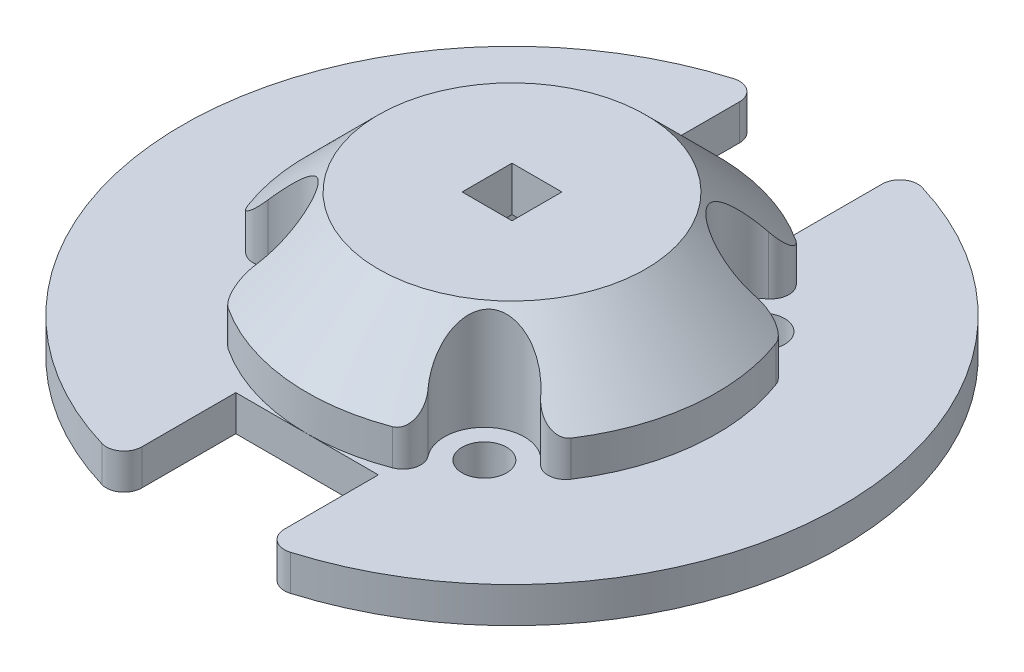
SolidWorks part; units mm, degrees
ref_plane "Front" through (0, 0, 0) normal (0, 0, 1) x (1, 0, 0)
ref_plane "Top" through (0, 0, 0) normal (0, 1, 0) x (1, 0, 0)
ref_plane "Right" through (0, 0, 0) normal (1, 0, 0) x (0, 0, -1)
sketch "Sketch1" plane through (0, 0, 0) normal (0, 1, 0) x (1, 0, 0)
  circle A0 centre (0, 0) radius 12.5
  dimension "D1" = 25
extrude "Boss-Extrude1" add sketch "Sketch1" along normal blind 2
sketch "Sketch2" plane through (0, 2, 0) normal (0, 1, 0) x (1, 0, 0)
  circle A0 centre (0, 0) radius 11.5
  dimension "D1" = 23
extrude "Boss-Extrude2" add sketch "Sketch2" along normal blind 6
sketch "Sketch3" plane through (0, 8, 0) normal (0, 1, 0) x (1, 0, 0)
  line L1 (-1.4, 1.4) -> (1.4, 1.4)
  line L2 (-1.4, 1.4) -> (-1.4, -1.4)
  line L3 (-1.4, -1.4) -> (1.4, -1.4)
  line L4 (1.4, 1.4) -> (1.4, -1.4)
  line L5 (-1.4, 1.4) -> (1.4, -1.4) construction
  line L6 (-1.4, -1.4) -> (1.4, 1.4) construction
  point P0 (0, 0)
  dimension "D1" = 2.8
  dimension "D2" = 2.8
hole_wizard "Ø2.5mm Dowel Hole1" positions "Sketch4" profile "Sketch6" hole size "Ø2.5" standard "DIN" end condition through all
sketch "Sketch4" plane through (0, 0, 0) normal (0, -1, 0) x (-1, 0, 0)
  point P0 (-6.2522, -7.8045)
  dimension "D1" = 10
sketch "Sketch6" plane through (6.2522, 0, 7.8045) normal (1, 0, 0) x (0, 0, -1)
  line L0 (0, 0) -> (0, 8)
  line L1 (0, 8) -> (1.25, 8)
  line L2 (1.25, 8) -> (1.25, 0)
  line L5 (1.25, 0) -> (0, 0)
  line L11 (0, -6.35) -> (0, 107.95) construction
  dimension "Thru Hole Dia." = 2.5
  dimension "Thru Hole Depth" = 8
sketch "Sketch7" plane through (0, 2, 0) normal (0, 1, 0) x (1, 0, 0)
  circle A0 centre (6.2522, -7.8045) radius 2.25
  dimension "D1" = 4.5
extrude "Cut-Extrude1" cut sketch "Sketch7" along normal blind 15
pattern_circular "CirPattern1" count 4 every 90 about axis through (0, 2, 0) along (0, -1, 0) of "Ø2.5mm Dowel Hole1", "Cut-Extrude1" reverse direction yes
sketch "Sketch8" plane through (0, 0, 0) normal (0, -1, 0) x (1, 0, 0)
  circle A0 centre (0, 0) radius 7.7
  dimension "D1" = 15.4
extrude "Cut-Extrude2" cut sketch "Sketch8" against normal blind 3.5
chamfer "Chamfer4" distance 4 angle 45 4 edges at (-1.2622, 8, 11.4305) (-11.4305, 8, -1.2622) (1.2622, 8, -11.4305) (11.4305, 8, 1.2622)
extrude "Cut-Extrude3" cut sketch "Sketch3" against normal through all
sketch "Sketch9" plane through (0, 3.5, 0) normal (0, -1, 0) x (1, 0, 0)
  circle A0 centre (0, 0) radius 5
  dimension "D1" = 10
extrude "Cut-Extrude4" cut sketch "Sketch9" against normal blind 2
fillet "Fillet1" radius 1 8 edges at (-7.7444, 3, 8.5014) (-9.9864, 3, 5.7029) (-8.5014, 3, -7.7444) (-5.7029, 3, -9.9864) (7.7444, 3, -8.5014) (9.9864, 3, -5.7029) (8.5014, 3, 7.7444) (5.7029, 3, 9.9864)
sketch "Sketch11" plane through (0, 0, 0) normal (1, 0, 0) x (0, 0, -1)
  line L0 (12.5, 0) -> (12.5, 2) construction
  line L1 (12.5, 0) -> (18.5, 0)
  line L2 (12.5, 0) -> (12.5, 2)
  line L3 (12.5, 2) -> (18.5, 2)
  line L4 (18.5, 0) -> (18.5, 2)
  dimension "D1" = 2
  dimension "D2" = 6
sketch "Sketch12" plane through (0, 0, 0) normal (1, 0, 0) x (0, 0, -1)
  line L0 (0, 0) -> (0, 14.0963)
revolve "Revolve1" add sketch "Sketch11" angle 360 about L0
sketch "Sketch13" plane through (0, 2, 0) normal (0, 1, 0) x (1, 0, 0)
  line L5 (-4, 11.5) -> (4, 11.5)
  line L6 (4, 11.5) -> (4, 21.8276)
  line L7 (-4, 21.8276) -> (4, 21.8276)
  line L8 (-4, 11.5) -> (-4, 21.8276)
  line L9 (-4, -21.8276) -> (4, -21.8276)
  line L10 (-4, -11.5) -> (-4, -21.8276)
  line L11 (-4, -11.5) -> (4, -11.5)
  line L12 (4, -11.5) -> (4, -21.8276)
  arc A2 (6.3089, 9.615) -> (-4.059, 10.7599) centre (0, 0) ccw construction
  point P11 (0, 11.5)
  dimension "D1" = 4
extrude "Cut-Extrude5" cut sketch "Sketch13" against normal blind 10
fillet "Fillet2" radius 1 4 edges at (4, 1, 18.0624) (-4, 1, 18.0624) (-4, 1, -18.0624) (4, 1, -18.0624)
